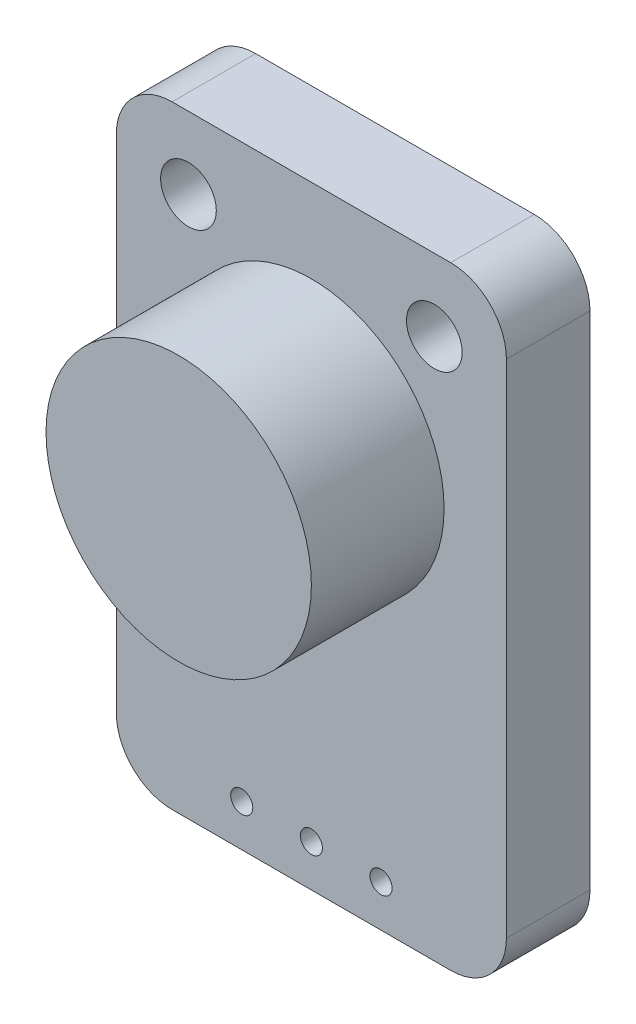
SolidWorks part; units mm, degrees
ref_plane "Front Plane" through (0, 0, 0) normal (0, 0, 1) x (1, 0, 0)
ref_plane "Top Plane" through (0, 0, 0) normal (0, 1, 0) x (1, 0, 0)
ref_plane "Right Plane" through (0, 0, 0) normal (1, 0, 0) x (0, 0, -1)
sketch "Sketch1" plane through (0, 0, 0) normal (0, 0, 1) x (1, 0, 0)
  line L0 (0, 4.7625) -> (-17.2472, 4.7625) construction
  line L1 (-7, -14.2375) -> (7, -14.2375)
  line L2 (-7, -14.2375) -> (-7, 7.7625)
  line L3 (-7, 7.7625) -> (7, 7.7625)
  line L4 (7, -14.2375) -> (7, 7.7625)
  line L5 (-7, -14.2375) -> (7, 7.7625) construction
  line L6 (-7, 7.7625) -> (7, -14.2375) construction
  circle A0 centre (0, 0) radius 4.7625
  point P3 (0, -3.2375)
  dimension "D1" = 9.525
  dimension "D2" = 22
  dimension "D3" = 14
  dimension "D4" = 3
extrude "Boss-Extrude1" add sketch "Sketch1" along normal blind 4.7625 contours A0 region at (0, 0, 0)
extrude "Boss-Extrude2" add sketch "Sketch1<3>" against normal blind 3 contours A0 | L1 L4 L3 L2 A0 region at (-6.7392, -3.2375, 0) region at (0, 0, 0)
sketch "Sketch1<3>" plane through (0, 0, 0) normal (0, 0, 1) x (1, 0, 0) same geometry as "Sketch1"
fillet "Fillet1" radius 2 4 edges at (-7, -14.2375, -1.5) (-7, 7.7625, -1.5) (7, -14.2375, -1.5) (7, 7.7625, -1.5)
sketch "Sketch2" plane through (0, 0, 0) normal (0, 0, 1) x (1, 0, 0)
  line L0 (-2.5, -12.7375) -> (0, -12.7375) construction
  line L1 (0, -12.7375) -> (2.5, -12.7375) construction
  line L2 (-5, -14.2375) -> (5, -14.2375) construction
  line L3 (-4.4125, 5.175) -> (4.4125, 5.175) construction
  line L4 (-4.4125, 6.175) -> (4.4125, 6.175) construction
  line L5 (-5.4125, 5.175) -> (-5.4125, 0.8073) construction
  line L6 (-7, -12.2375) -> (-7, 5.7625) construction
  line L7 (-5, 7.7625) -> (5, 7.7625) construction
  circle A0 centre (0, -12.7375) radius 0.3969
  circle A1 centre (2.5, -12.7375) radius 0.3969
  circle A2 centre (-2.5, -12.7375) radius 0.3969
  circle A3 centre (-4.4125, 5.175) radius 1
  circle A4 centre (4.4125, 5.175) radius 1
  point P21 (0, 5.175)
  dimension "D1" = 0.7937
  dimension "D2" = 2
  dimension "D3" = 1.5
  dimension "D4" = 5
  dimension "D5" = 1.5875
  dimension "D6" = 1.5875
extrude "Cut-Extrude1" cut sketch "Sketch2" against normal through all both and the other way through all
